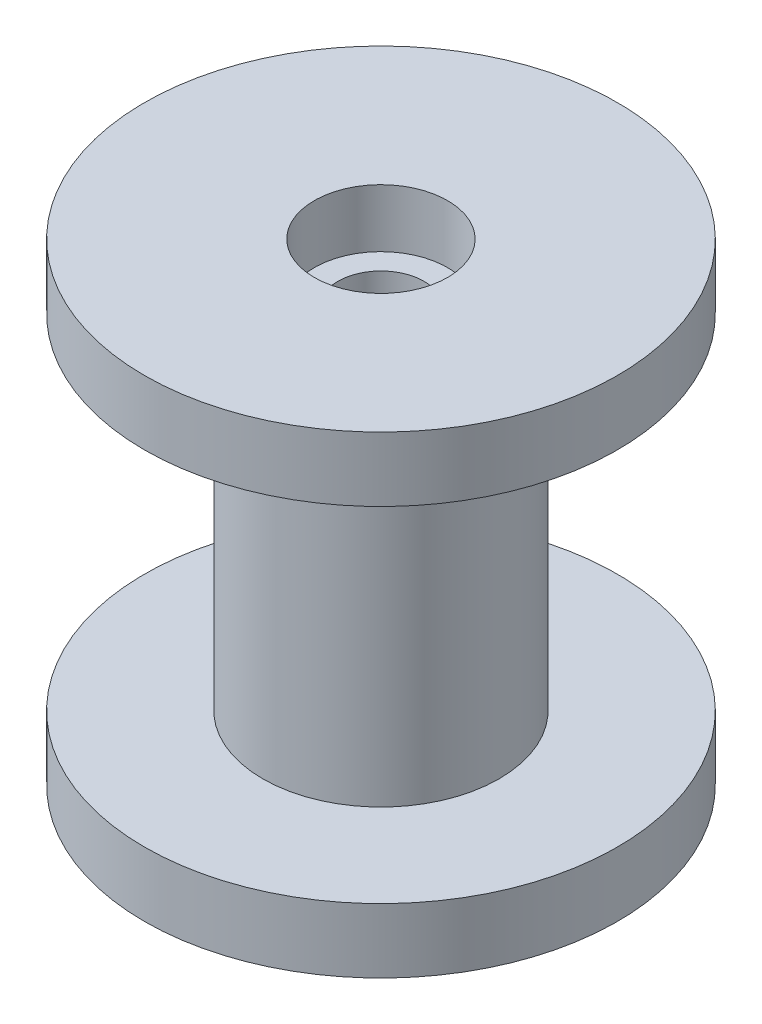
SolidWorks part; units mm, degrees
ref_plane "前视基准面" through (0, 0, 0) normal (0, 0, 1) x (1, 0, 0)
ref_plane "上视基准面" through (0, 0, 0) normal (0, 1, 0) x (1, 0, 0)
ref_plane "右视基准面" through (0, 0, 0) normal (1, 0, 0) x (0, 0, -1)
other "Configuration Table"
sketch "草图1" plane through (0, 0, 0) normal (0, 1, 0) x (1, 0, 0)
  circle A0 centre (0, 0) radius 5.5
  circle A1 centre (0, 0) radius 11
  dimension "D1" = 5.5
  dimension "D2" = 22
extrude "凸台-拉伸3" add sketch "草图1" along normal mid plane 22 contours A1
extrude "切除-拉伸1" cut sketch "草图1<10>" along normal mid plane 16
sketch "草图1<10>" plane through (0, 0, 0) normal (0, 1, 0) x (1, 0, 0) same geometry as "草图1"
sketch "草图2" plane through (0, 11, 0) normal (0, 1, 0) x (1, 0, 0)
  circle A0 centre (0, 0) radius 3.1
  circle A1 centre (0, 0) radius 2
  point P3 (0, 0)
  point P4 (-6.8749, 2.3762)
  point P6 (0, 0)
  dimension "D1" = 4
  dimension "D2" = 6.2
extrude "切除-拉伸2" cut sketch "草图2" against normal through all contours A1
extrude "切除-拉伸3" cut sketch "草图2<3>" against normal blind 2.7 contours A0
sketch "草图2<3>" plane through (0, 11, 0) normal (0, 1, 0) x (1, 0, 0) same geometry as "草图2"
extrude "切除-拉伸4" cut sketch "草图2<4>" along normal blind 2.7 from surface contours A0 starting at face at (0, -11, 2)
sketch "草图2<4>" plane through (0, 11, 0) normal (0, 1, 0) x (1, 0, 0) same geometry as "草图2"
